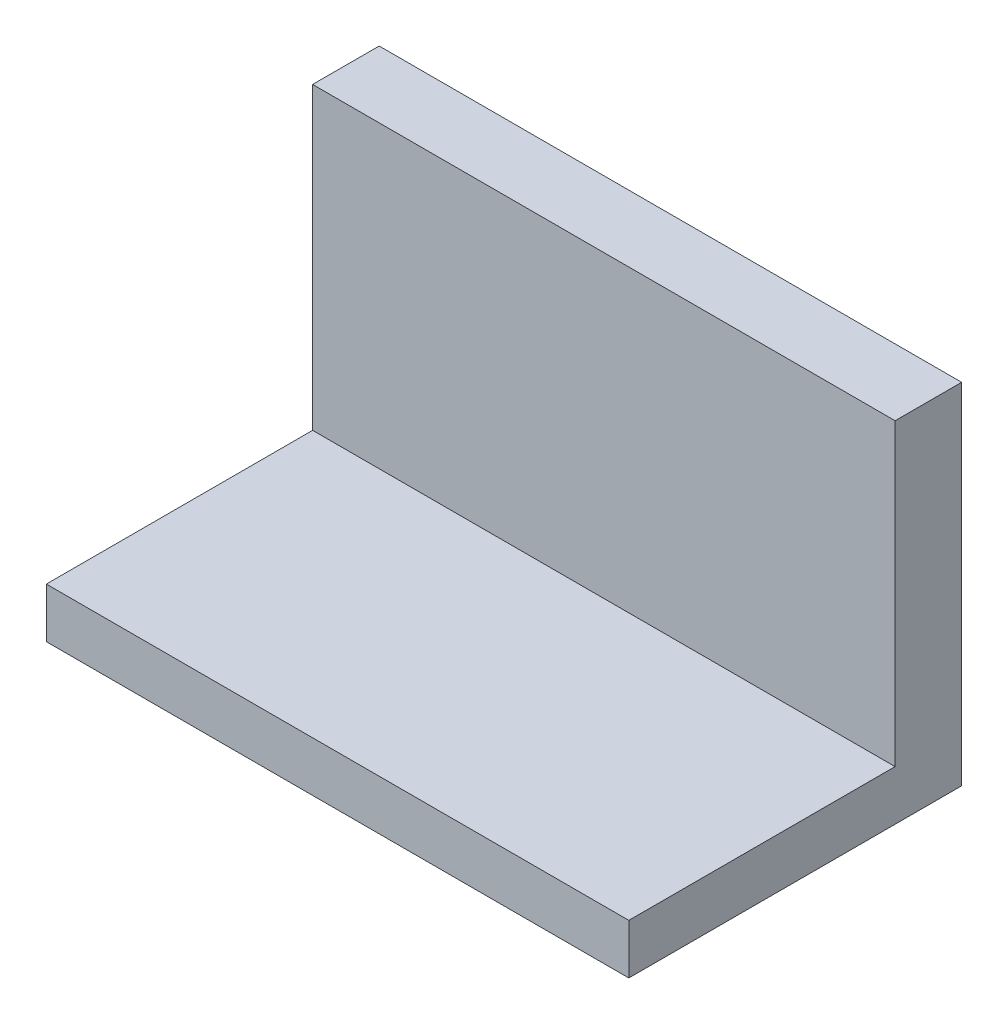
SolidWorks part; units mm, degrees
ref_plane "Front Plane" through (0, 0, 0) normal (0, 0, 1) x (1, 0, 0)
ref_plane "Top Plane" through (0, 0, 0) normal (0, 1, 0) x (1, 0, 0)
ref_plane "Right Plane" through (0, 0, 0) normal (1, 0, 0) x (0, 0, -1)
sketch "Sketch1" plane through (0, 0, 0) normal (0, 1, 0) x (1, 0, 0)
  line L1 (-17.5, -10) -> (17.5, -10)
  line L2 (-17.5, -10) -> (-17.5, 10)
  line L3 (-17.5, 10) -> (17.5, 10)
  line L4 (17.5, -10) -> (17.5, 10)
  line L5 (-17.5, -10) -> (17.5, 10) construction
  line L6 (-17.5, 10) -> (17.5, -10) construction
  line L7 (17.5, 10) -> (-17.5, 10)
  line L8 (17.5, 10) -> (17.5, 6)
  line L9 (17.5, 6) -> (-17.5, 6)
  line L10 (-17.5, 10) -> (-17.5, 6)
  point P0 (0, 0)
  dimension "D1" = 35
  dimension "D2" = 20
  dimension "D3" = 4
extrude "Boss-Extrude1" add sketch "Sketch1" along normal blind 3 contours L9 L4 L3 L2 | L4 L9 L2 L1 region at (0, 0, 2) region at (0, 0, -8)
extrude "Boss-Extrude2" add sketch "Sketch1<3>" along normal blind 21 contours L9 L4 L3 L2 region at (0, 0, -8)
sketch "Sketch1<3>" plane through (0, 0, 0) normal (0, 1, 0) x (1, 0, 0) same geometry as "Sketch1"
sketch "Sketch2" plane through (0, 0, -10) normal (0, 0, -1) x (-1, 0, 0)
  line L0 (-10, 16) -> (10, 16)
  line L1 (17.5, 21) -> (-17.5, 21) construction
  line L2 (-7.7985, 16) -> (7.7985, 16) construction
  line L3 (-7.7985, 18.1) -> (7.7985, 18.1)
  line L4 (-7.7985, 13.9) -> (7.7985, 13.9)
  arc A0 (-7.7985, 18.1) -> (-7.7985, 13.9) centre (-7.7985, 16) ccw
  arc A1 (7.7985, 13.9) -> (7.7985, 18.1) centre (7.7985, 16) ccw
  point P3 (0, 16)
  point P8 (0, 16)
  dimension "D1" = 20
  dimension "D2" = 0
  dimension "D3" = 5
  dimension "D4" = 4.2
